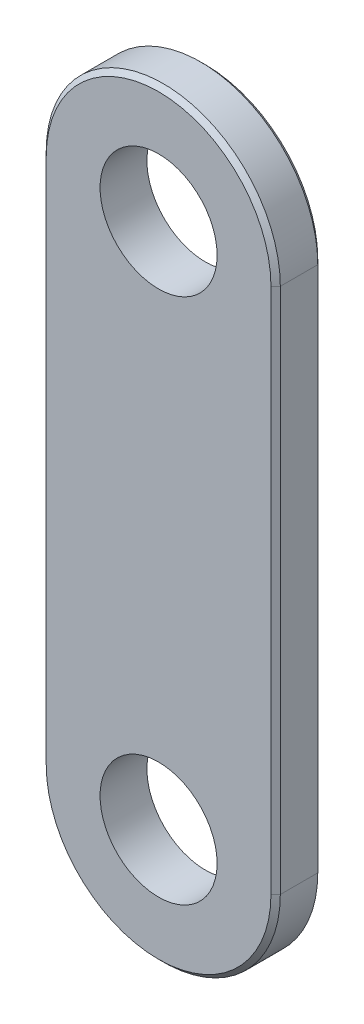
SolidWorks part; units mm, degrees
ref_plane "Front Plane" through (0, 0, 0) normal (0, 0, 1) x (1, 0, 0)
ref_plane "Top Plane" through (0, 0, 0) normal (0, 1, 0) x (1, 0, 0)
ref_plane "Right Plane" through (0, 0, 0) normal (1, 0, 0) x (0, 0, -1)
sketch "Sketch1" plane through (0, 0, 0) normal (0, 0, 1) x (1, 0, 0)
  line L0 (-50, 111.4754) -> (-50, -113.5246)
  line L1 (50, 111.4754) -> (50, -113.5246)
  arc A0 (50, 111.4754) -> (-50, 111.4754) centre (0, 111.4754) ccw
  arc A1 (-50, -113.5246) -> (50, -113.5246) centre (0, -113.5246) ccw
  circle A2 centre (0, 111.4754) radius 25
  circle A3 centre (0, -113.5246) radius 25
  dimension "D1" = 100
  dimension "D2" = 100
  dimension "D4" = 50
  dimension "D5" = 50
  dimension "D3" = 225
extrude "Boss-Extrude1" add sketch "Sketch1" along normal blind 20 contours L1 A1 L0 A0
extrude "Cut-Extrude1" cut sketch "Sketch1<3>" along normal blind 149 contours A2 | A3
sketch "Sketch1<3>" plane through (0, 0, 0) normal (0, 0, 1) x (1, 0, 0) same geometry as "Sketch1"
chamfer "Chamfer1" distance 2 angle 45 8 edges at (0, -163.5246, 0) (-50, -1.0246, 0) (0, 161.4754, 0) (50, -1.0246, 0) (0, -163.5246, 20) (-50, -1.0246, 20) (0, 161.4754, 20) (50, -1.0246, 20)
